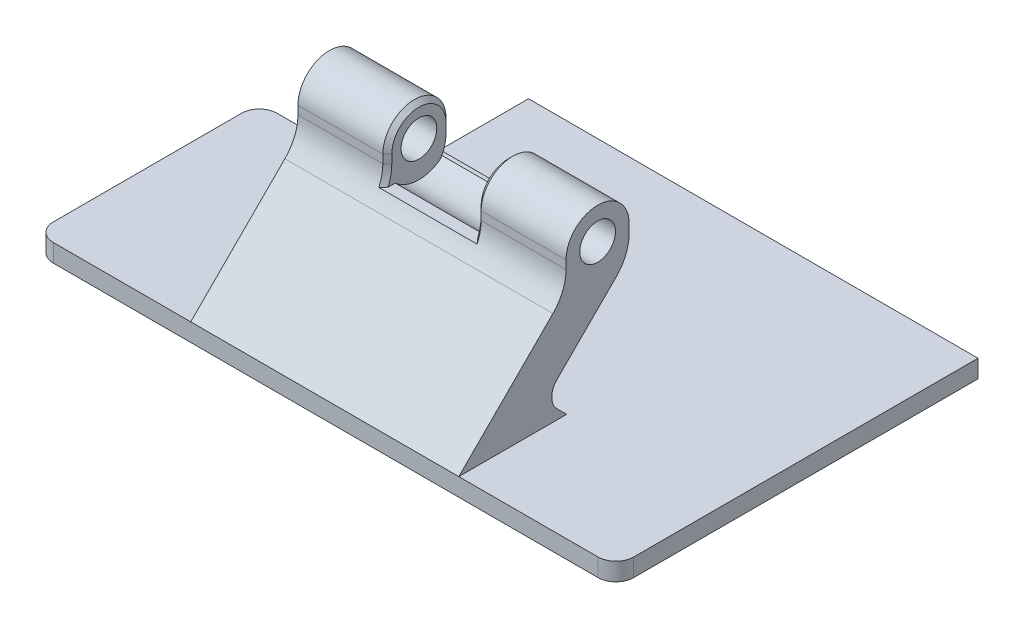
SolidWorks part; units mm, degrees
ref_plane "Front Plane" through (0, 0, 0) normal (0, 0, 1) x (1, 0, 0)
ref_plane "Top Plane" through (0, 0, 0) normal (0, 1, 0) x (1, 0, 0)
ref_plane "Right Plane" through (0, 0, 0) normal (1, 0, 0) x (0, 0, -1)
sketch "Sketch1" plane through (0, 0, 0) normal (0, 1, 0) x (1, 0, 0)
  line L0 (-30.372, 4.8519) -> (-20.222, 4.8519)
  line L5 (-30.372, -20.1981) -> (30.578, -20.1981)
  line L6 (-32.372, -18.1981) -> (-32.372, 2.8519)
  line L7 (-17.722, 20.3266) -> (32.578, 20.3266)
  line L16 (32.578, -18.1981) -> (32.578, 20.3266)
  line L17 (-32.372, -20.1981) -> (32.578, 20.3266) construction
  line L18 (-17.722, 10.9875) -> (32.578, -20.1981) construction
  line L19 (-17.722, 7.3519) -> (-17.722, 20.3266)
  arc A0 (30.578, -20.1981) -> (32.578, -18.1981) centre (30.578, -18.1981) ccw
  arc A1 (-30.372, -20.1981) -> (-32.372, -18.1981) centre (-30.372, -18.1981) cw
  arc A2 (-30.372, 4.8519) -> (-32.372, 2.8519) centre (-30.372, 2.8519) ccw
  arc A3 (-20.222, 4.8519) -> (-17.722, 7.3519) centre (-20.222, 7.3519) ccw
  point P0 (0, 0)
  dimension "D1" = 25.05
  dimension "D5" = 14.65
  dimension "D3" = 2
  dimension "D4" = 2.5
  dimension "D2" = 64.95
  dimension "D6" = 50.3
extrude "Boss-Extrude2" add sketch "Sketch1" along normal blind 2
sketch "Sketch2" plane through (0, 0, 0) normal (1, 0, 0) x (0, 0, -1)
  line L0 (-20.1981, 2) -> (-8.1981, 14) construction
  line L1 (-18.1981, 2) -> (20.3266, 2) construction
  line L2 (-20.1981, 2) -> (-8.1981, 14)
  line L4 (-1.1271, 14) -> (-13.1271, 2)
  line L5 (-13.1271, 2) -> (-20.1981, 2)
  line L9 (-8.1981, 14) -> (-8.1981, 17)
  line L11 (-1.1271, 14) -> (-1.1271, 17)
  arc A0 (-8.1981, 17) -> (-1.1271, 17) centre (-4.6626, 17) cw
  circle A1 centre (-4.6626, 17) radius 2
  dimension "D3" = 3.5355
  dimension "D4" = 4
  dimension "D1" = 45
  dimension "D2" = 45
  dimension "D5" = 3
  dimension "D6" = 7.0711
extrude "Boss-Extrude3" add sketch "Sketch2" along normal mid plane 30
chamfer "Chamfer1" distance 5 angle 45 1 edges at (0, 2, 13.1271) first distance on face at (-6.094, 2, 5.9867)
fillet "Fillet2" radius 5 2 edges at (0, 14, 8.1981) (0, 14, 1.1271)
fillet "Fillet3" radius 2 1 edges at (0, 4.5, 10.6271)
sketch "Sketch4" plane through (0, 0, 0) normal (1, 0, 0) x (0, 0, -1)
  circle A0 centre (-4.6626, 17) radius 4
extrude "Cut-Extrude2" cut sketch "Sketch4" against normal mid plane 10
sketch "Sketch5" plane through (0, 0, 0) normal (0, 0, 1) x (1, 0, 0)
  line L1 (-5, 17) -> (5, 17)
  line L2 (-5, 17) -> (-5, 14)
  line L3 (-5, 14) -> (5, 14)
  line L4 (5, 17) -> (5, 14)
extrude "Cut-Extrude4" cut sketch "Sketch5" along normal blind 40
chamfer "Chamfer2" distance 0.5 angle 45 10 edges at (5, 15.0115, 1.2406) (5, 15.0115, 8.3117) (5, 16.5355, 1.1271) (5, 16.5355, 8.1981) (5, 20.5355, 4.6626) (-5, 15.0115, 1.2406) (-5, 15.0115, 8.3117) (-5, 16.5355, 1.1271) (-5, 16.5355, 8.1981) (-5, 20.5355, 4.6626)
